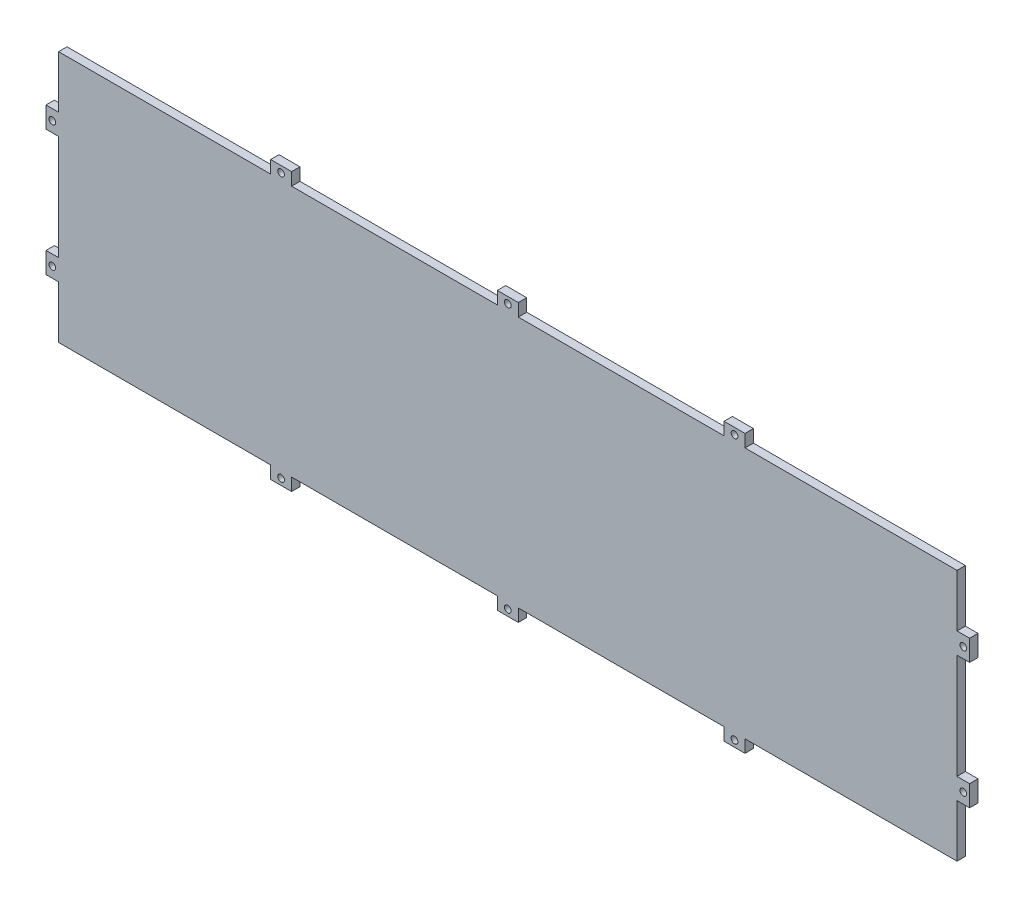
SolidWorks part; units mm, degrees
ref_plane "Front Plane" through (0, 0, 0) normal (0, 0, 1) x (1, 0, 0)
ref_plane "Top Plane" through (0, 0, 0) normal (0, 1, 0) x (1, 0, 0)
ref_plane "Right Plane" through (0, 0, 0) normal (1, 0, 0) x (0, 0, -1)
sketch "Sketch1" plane through (0, 0, 0) normal (0, 0, 1) x (1, 0, 0)
  line L0 (110.4, 127) -> (113.6, 127) construction
  line L1 (6, 250) -> (107, 250)
  line L2 (6, 250) -> (6, 225)
  line L3 (6, 130) -> (107, 130)
  line L4 (434, 250) -> (434, 225)
  line L5 (110.4, 130) -> (110.4, 124) construction
  line L6 (113.6, 124) -> (113.6, 130) construction
  line L7 (218.4, 127) -> (221.6, 127) construction
  line L8 (218.4, 130) -> (218.4, 124) construction
  line L9 (221.6, 124) -> (221.6, 130) construction
  line L10 (326.4, 127) -> (329.6, 127) construction
  line L11 (326.4, 130) -> (326.4, 124) construction
  line L12 (329.6, 124) -> (329.6, 130) construction
  line L13 (117, 130) -> (215, 130)
  line L14 (107, 124) -> (117, 124)
  line L15 (107, 124) -> (107, 130)
  line L16 (225, 130) -> (323, 130)
  line L17 (117, 124) -> (117, 130)
  line L18 (107, 124) -> (117, 130) construction
  line L19 (107, 130) -> (117, 124) construction
  line L20 (215, 124) -> (225, 124)
  line L21 (215, 124) -> (215, 130)
  line L22 (333, 130) -> (434, 130)
  line L23 (225, 124) -> (225, 130)
  line L24 (215, 124) -> (225, 130) construction
  line L25 (215, 130) -> (225, 124) construction
  line L26 (323, 124) -> (333, 124)
  line L27 (323, 124) -> (323, 130)
  line L28 (6, 190) -> (434, 190) construction
  line L29 (333, 124) -> (333, 130)
  line L30 (323, 124) -> (333, 130) construction
  line L31 (323, 130) -> (333, 124) construction
  line L32 (323, 256) -> (323, 250)
  line L33 (323, 256) -> (333, 256)
  line L34 (333, 256) -> (333, 250)
  line L35 (215, 256) -> (215, 250)
  line L36 (215, 256) -> (225, 256)
  line L37 (225, 256) -> (225, 250)
  line L38 (107, 256) -> (107, 250)
  line L39 (117, 256) -> (117, 250)
  line L40 (107, 256) -> (117, 256)
  line L41 (333, 250) -> (434, 250)
  line L42 (225, 250) -> (323, 250)
  line L43 (117, 250) -> (215, 250)
  line L44 (0, 250) -> (6, 190) construction
  line L45 (6, 215) -> (6, 165)
  line L46 (0, 215) -> (6, 215)
  line L47 (0, 215) -> (0, 225)
  line L48 (0, 225) -> (6, 225)
  line L49 (0, 250) -> (0, 225) construction
  line L50 (0, 215) -> (6, 225) construction
  line L51 (0, 225) -> (6, 215) construction
  line L52 (0, 155) -> (6, 155)
  line L53 (0, 165) -> (0, 155)
  line L54 (0, 165) -> (6, 165)
  line L55 (220, 190) -> (220, 221.6948) construction
  line L56 (440, 165) -> (434, 165)
  line L57 (440, 165) -> (440, 155)
  line L58 (440, 155) -> (434, 155)
  line L59 (440, 215) -> (434, 215)
  line L60 (440, 215) -> (440, 225)
  line L61 (440, 225) -> (434, 225)
  line L62 (6, 155) -> (6, 130)
  line L63 (434, 155) -> (434, 130)
  line L64 (434, 215) -> (434, 165)
  circle A0 centre (112, 127) radius 1.6
  circle A1 centre (220, 127) radius 1.6
  circle A2 centre (328, 127) radius 1.6
  circle A3 centre (328, 253) radius 1.6
  circle A4 centre (220, 253) radius 1.6
  circle A5 centre (112, 253) radius 1.6
  circle A6 centre (3, 220) radius 1.6
  circle A7 centre (3, 160) radius 1.6
  circle A8 centre (437, 220) radius 1.6
  circle A9 centre (437, 160) radius 1.6
  point P24 (112, 127)
  point P29 (220, 127)
  point P34 (328, 127)
  point P47 (107, 127)
  point P66 (107, 253)
  point P68 (3, 220)
  dimension "D3" = 3.2
  dimension "D1" = 10
  dimension "D2" = 10
extrude "Boss-Extrude1" add sketch "Sketch1" against normal blind 4
